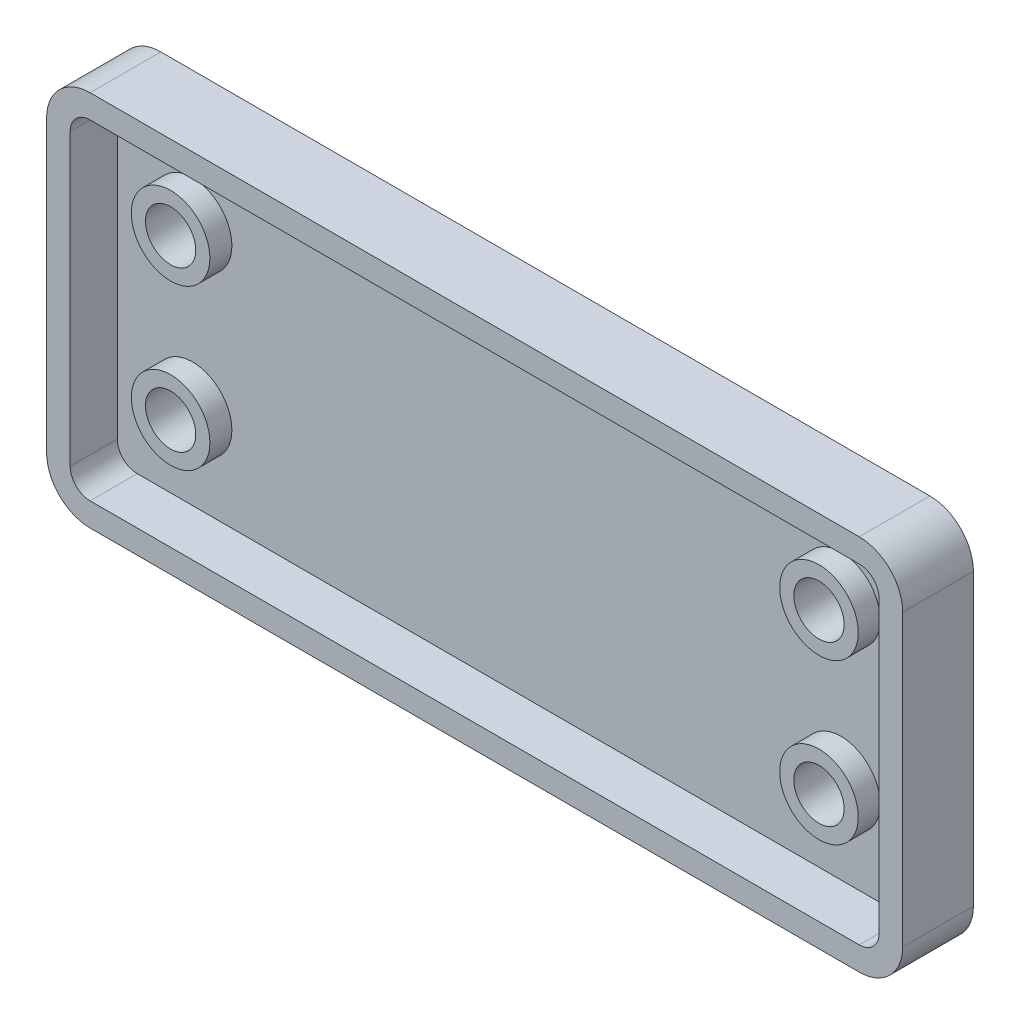
SolidWorks part; units mm, degrees
ref_plane "Plan de face" through (0, 0, 0) normal (0, 0, 1) x (1, 0, 0)
ref_plane "Plan de dessus" through (0, 0, 0) normal (0, 1, 0) x (1, 0, 0)
ref_plane "Plan de droite" through (0, 0, 0) normal (1, 0, 0) x (0, 0, -1)
sketch "Esquisse1" plane through (0, 0, 0) normal (0, 0, 1) x (1, 0, 0)
  line L1 (-24.48, -10.5) -> (24.48, -10.5)
  line L2 (-25.75, -9.23) -> (-25.75, 9.23)
  line L3 (-24.48, 10.5) -> (24.48, 10.5)
  line L4 (25.75, -9.23) -> (25.75, 9.23)
  line L5 (-25.75, -10.5) -> (25.75, 10.5) construction
  line L6 (-25.75, 10.5) -> (25.75, -10.5) construction
  arc A0 (24.48, -10.5) -> (25.75, -9.23) centre (24.48, -9.23) ccw
  arc A1 (-24.48, -10.5) -> (-25.75, -9.23) centre (-24.48, -9.23) cw
  arc A2 (-25.75, 9.23) -> (-24.48, 10.5) centre (-24.48, 9.23) cw
  arc A3 (24.48, 10.5) -> (25.75, 9.23) centre (24.48, 9.23) cw
  point P0 (0, 0)
  dimension "D3" = 1.27
  dimension "D1" = 51.5
  dimension "D2" = 21
extrude "Boss.-Extru.1" add sketch "Esquisse1" along normal blind 3
shell "Coque1" thickness 1.5 removed face at (0, 0, 3) outward yes
ref_plane "PlanMedian" through (0, 0, 0) normal (0, 1, 0) x (1, 0, 0)
ref_plane "PlanSagital" through (0, 0, 0) normal (-1, 0, 0) x (0, 0, 1)
sketch "Esquisse2" plane through (0, 0, 0) normal (0, 0, 1) x (1, 0, 0)
  circle A0 centre (-20.955, 5.08) radius 1.6
  circle A1 centre (-20.955, -5.08) radius 1.6
  circle A2 centre (20.32, 5.08) radius 1.6
  circle A3 centre (20.32, -5.08) radius 1.6
  circle A5 centre (20.32, 5.08) radius 2.5
  circle A6 centre (-20.955, -5.08) radius 2.5
  circle A7 centre (-20.955, 5.08) radius 2.5
  circle A8 centre (20.32, -5.08) radius 2.5
  dimension "D1" = 5
extrude "Boss.-Extru.2" add sketch "Esquisse2" along normal blind 1.4
sketch "Esquisse3" plane through (0, 0, 0) normal (0, 0, 1) x (1, 0, 0)
  circle A0 centre (20.32, 5.08) radius 1.6
  circle A1 centre (-20.955, 5.08) radius 1.6
  circle A2 centre (-20.955, -5.08) radius 1.6
  circle A3 centre (20.32, -5.08) radius 1.6
extrude "Enlèv. mat.-Extru.1" cut sketch "Esquisse3" against normal through all both and the other way through all
